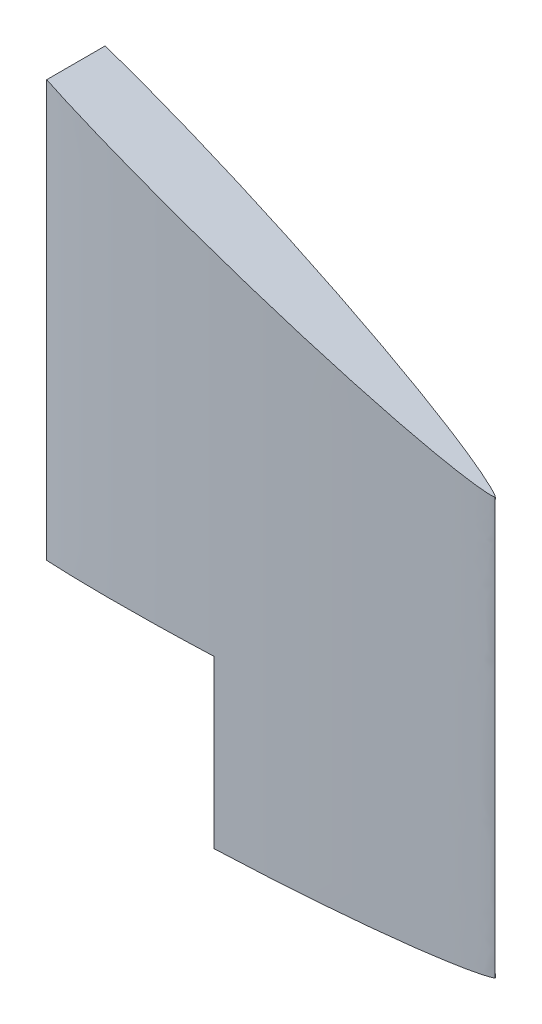
SolidWorks part; units mm, degrees
ref_plane "前视基准面" through (0, 0, 0) normal (0, 0, 1) x (1, 0, 0)
ref_plane "上视基准面" through (0, 0, 0) normal (0, 1, 0) x (1, 0, 0)
ref_plane "右视基准面" through (0, 0, 0) normal (1, 0, 0) x (0, 0, -1)
other "Configuration Table"
sketch "草图1" plane through (0, 0, 0) normal (0, 1, 0) x (1, 0, 0)
  line L0 (-2000, 0) -> (98000, 0) construction
  line L1 (0, -2000) -> (0, 98000) construction
  line L2 (0, 3.5) -> (0, -3.5)
  spline S0 degree 4 poles (50.3662, 0) (50.3616, -0.0076) (50.3512, -0.0201) (50.3319, -0.0346) (50.3036, -0.0542) (50.2676, -0.0756) (50.2125, -0.105) (50.1197, -0.1486) (49.9578, -0.2148) (49.6652, -0.3175) (49.1393, -0.4735) (48.2702, -0.6887) (46.7082, -1.0116) (44.5066, -1.3804) (41.7789, -1.7599) (38.6521, -2.1248) (35.5143, -2.4387) (32.3724, -2.71) (29.2277, -2.9446) (26.0806, -3.1456) (22.9317, -3.3152) (19.7813, -3.4544) (16.6297, -3.5633) (13.4772, -3.6409) (10.324, -3.6857) (7.1705, -3.6936) (4.1946, -3.6609) (2.0077, -3.5999) (0.6097, -3.5385) (0, -3.5) knots 0 0 0 0 0 0.000699 0.001288 0.00188 0.002733 0.003996 0.006219 0.009974 0.016536 0.028475 0.049524 0.080651 0.142462 0.204716 0.26697 0.329223 0.391477 0.453731 0.515984 0.578238 0.640492 0.702745 0.764999 0.827253 0.889506 0.95176 1 1 1 1 1 construction
  spline S1 degree 4 poles (50.3662, 0) (50.3616, -0.0076) (50.3512, -0.0201) (50.3319, -0.0346) (50.3036, -0.0542) (50.2676, -0.0756) (50.2125, -0.105) (50.1197, -0.1486) (49.9578, -0.2148) (49.6652, -0.3175) (49.1393, -0.4735) (48.2702, -0.6887) (46.7082, -1.0116) (44.5066, -1.3804) (41.7789, -1.7599) (38.6521, -2.1248) (35.5143, -2.4387) (32.3724, -2.71) (29.2277, -2.9446) (26.0806, -3.1456) (22.9317, -3.3152) (19.7813, -3.4544) (16.6297, -3.5633) (13.4772, -3.6409) (10.324, -3.6857) (7.1705, -3.6936) (4.1946, -3.6609) (2.0077, -3.5999) (0.6097, -3.5385) (0, -3.5) knots 0 0 0 0 0 0.000699 0.001288 0.00188 0.002733 0.003996 0.006219 0.009974 0.016536 0.028475 0.049524 0.080651 0.142462 0.204716 0.26697 0.329223 0.391477 0.453731 0.515984 0.578238 0.640492 0.702745 0.764999 0.827253 0.889506 0.95176 1 1 1 1 1
  spline S2 degree 4 poles (50.3662, 0) (50.3616, 0.0076) (50.3512, 0.0201) (50.3319, 0.0346) (50.3036, 0.0542) (50.2676, 0.0756) (50.2125, 0.105) (50.1197, 0.1486) (49.9578, 0.2148) (49.6652, 0.3175) (49.1393, 0.4735) (48.2702, 0.6887) (46.7082, 1.0116) (44.5066, 1.3804) (41.7789, 1.7599) (38.6521, 2.1248) (35.5143, 2.4387) (32.3724, 2.71) (29.2277, 2.9446) (26.0806, 3.1456) (22.9317, 3.3152) (19.7813, 3.4544) (16.6297, 3.5633) (13.4772, 3.6409) (10.324, 3.6857) (7.1705, 3.6936) (4.1946, 3.6609) (2.0077, 3.5999) (0.6097, 3.5385) (0, 3.5) knots 0 0 0 0 0 0.000699 0.001288 0.00188 0.002733 0.003996 0.006219 0.009974 0.016536 0.028475 0.049524 0.080651 0.142462 0.204716 0.26697 0.329223 0.391477 0.453731 0.515984 0.578238 0.640492 0.702745 0.764999 0.827253 0.889506 0.95176 1 1 1 1 1
  point P8 (0, 0)
  dimension "D1" = 7
extrude "凸台-拉伸2" add sketch "草图1" along normal blind 100
sketch "草图3" plane through (0, 0, 0) normal (0, 0, 1) x (1, 0, 0)
  line L0 (50.3662, 100) -> (50.3662, 80)
  line L1 (50.3662, 80) -> (0, 100)
  line L2 (0, 100) -> (50.3662, 100)
  line L3 (-1000, 50) -> (49000, 50) construction
  line L4 (0, 0) -> (50.3662, 0)
  line L5 (50.3662, 0) -> (50.3662, 100)
  line L6 (50.3662, 100) -> (0, 100)
  line L7 (0, 100) -> (0, 0)
  line L8 (0, 0) -> (50.3662, 0) construction
  line L9 (50.3662, 0) -> (50.3662, 100) construction
  line L10 (50.3662, 100) -> (0, 100) construction
  line L11 (0, 100) -> (0, 0) construction
  line L12 (50.3662, 0) -> (50.3662, 20)
  line L13 (0, 0) -> (50.3662, 0)
  line L14 (50.3662, 20) -> (0, 0)
  point P8 (0, 50)
  dimension "D2" = 20
  dimension "D1" = 0
extrude "切除-拉伸1" cut sketch "草图3" against normal blind 100 and the other way blind 100
sketch "草图6" plane through (0, 0, 0) normal (0, 0, 1) x (1, 0, 0)
  line L0 (-1000, 50) -> (49000, 50) construction
  line L1 (0, 50) -> (20, 50)
  line L2 (20, 50) -> (20, 30)
  line L3 (20, 30) -> (50.3662, 30)
  line L4 (0, 0) -> (50.3662, 20)
  line L5 (50.3662, 20) -> (50.3662, 80)
  line L6 (50.3662, 80) -> (0, 100)
  line L7 (0, 100) -> (0, 0)
  line L8 (0, 0) -> (50.3662, 20) construction
  line L9 (50.3662, 20) -> (50.3662, 80) construction
  line L10 (50.3662, 80) -> (0, 100) construction
  line L11 (0, 100) -> (0, 0) construction
  line L12 (50.3662, 30) -> (50.3662, 20)
  line L13 (50.3662, 20) -> (0, 0)
  line L14 (0, 0) -> (0, 50)
  point P7 (0, 50)
  dimension "D2" = 20
  dimension "D3" = 20
  dimension "D1" = 0
extrude "切除-拉伸2" cut sketch "草图6" against normal blind 100 and the other way blind 100
sketch "草图7" plane through (0, 0, 0) normal (1, 0, 0) x (0, 0, -1)
  line L4 (-3.5, 50) -> (3.5, 50)
  line L5 (-3.5, 100) -> (-3.5, 50)
  line L6 (3.5, 100) -> (-3.5, 100)
  line L7 (3.5, 50) -> (3.5, 100)
  line L8 (-3.5, 50) -> (3.5, 50) construction
  line L9 (-3.5, 100) -> (-3.5, 50) construction
  line L10 (3.5, 100) -> (-3.5, 100) construction
  line L11 (3.5, 50) -> (3.5, 100) construction
  circle A0 centre (0, 50) radius 2.5
  dimension "D2" = 5
  dimension "D1" = 0
extrude "切除-拉伸3" cut sketch "草图7" along normal blind 4
sketch "草图9" plane through (0, 0, 0) normal (0, 1, 0) x (1, 0, 0)
  line L0 (20, -1) -> (20, 1)
  line L1 (20, 3.4394) -> (20, -3.4394)
  line L2 (20, 3.4394) -> (20, -3.4394) construction
  line L3 (20, -1) -> (25, -1)
  line L4 (25, -1) -> (25, 1)
  line L5 (25, 1) -> (20, 1)
  spline S2 degree 4 poles (-426.2359, 2951.1555) (-201.3053, 23.7335) (-133.4959, 13.9087) (-51.7327, -8.1154) (29.2277, -2.9446) (32.3724, -2.71) (35.5143, -2.4387) (38.6521, -2.1248) (41.7789, -1.7599) (44.5066, -1.3804) (46.7082, -1.0116) (48.2702, -0.6887) (49.1393, -0.4735) (49.6652, -0.3175) (49.9578, -0.2148) (50.1197, -0.1486) (50.2125, -0.105) (50.2676, -0.0756) (50.3036, -0.0542) (50.7698, 0.2686) (51.1351, 1.1537) (-54.7758, 79.9279) (2083.2834, -2198.4663) knots -5.735274 -5.735274 -5.735274 -5.735274 -5.735274 0.484016 0.546269 0.608523 0.670777 0.73303 0.795284 0.857538 0.919349 0.950476 0.971525 0.983464 0.990026 0.993781 0.996004 0.997267 0.99812 0.998712 0.999301 1.042246 1.042246 1.042246 1.042246 1.042246 only from (20, -3.4394) to (50.3662, 0)
  spline S3 degree 4 poles (2081.6696, 2196.7466) (-54.7167, -79.8839) (51.135, -1.1534) (50.7697, -0.2685) (50.3036, 0.0542) (50.2676, 0.0756) (50.2125, 0.105) (50.1197, 0.1486) (49.9578, 0.2148) (49.6652, 0.3175) (49.1393, 0.4735) (48.2702, 0.6887) (46.7082, 1.0116) (44.5066, 1.3804) (41.7789, 1.7599) (38.6521, 2.1248) (35.5143, 2.4387) (32.3724, 2.71) (29.2277, 2.9446) (-51.7329, 8.1154) (-133.4961, -13.9087) (-201.3057, -23.7336) (-426.2376, -2951.1767) knots -0.042237 -0.042237 -0.042237 -0.042237 -0.042237 0.000699 0.001288 0.00188 0.002733 0.003996 0.006219 0.009974 0.016536 0.028475 0.049524 0.080651 0.142462 0.204716 0.26697 0.329223 0.391477 0.453731 0.515984 6.735285 6.735285 6.735285 6.735285 6.735285 only from (50.3662, 0) to (20, 3.4394)
  spline S4 degree 4 poles (20, -3.4394) (21.1268, -3.3943) (23.0411, -3.3088) (25.7419, -3.1672) (29.2277, -2.9446) (32.3724, -2.71) (35.5143, -2.4387) (38.6521, -2.1248) (41.7789, -1.7599) (44.5066, -1.3804) (46.7082, -1.0116) (48.2702, -0.6887) (49.1393, -0.4735) (49.6652, -0.3175) (49.9578, -0.2148) (50.1197, -0.1486) (50.2125, -0.105) (50.2676, -0.0756) (50.3036, -0.0542) (50.3319, -0.0346) (50.3512, -0.0201) (50.3616, -0.0076) (50.3662, 0) knots 0.394961 0.394961 0.394961 0.394961 0.394961 0.484016 0.546269 0.608523 0.670777 0.73303 0.795284 0.857538 0.919349 0.950476 0.971525 0.983464 0.990026 0.993781 0.996004 0.997267 0.99812 0.998712 0.999301 1 1 1 1 1 construction
  spline S5 degree 4 poles (50.3662, 0) (50.3616, 0.0076) (50.3512, 0.0201) (50.3319, 0.0346) (50.3036, 0.0542) (50.2676, 0.0756) (50.2125, 0.105) (50.1197, 0.1486) (49.9578, 0.2148) (49.6652, 0.3175) (49.1393, 0.4735) (48.2702, 0.6887) (46.7082, 1.0116) (44.5066, 1.3804) (41.7789, 1.7599) (38.6521, 2.1248) (35.5143, 2.4387) (32.3724, 2.71) (29.2277, 2.9446) (25.7419, 3.1672) (23.0411, 3.3088) (21.1268, 3.3943) (20, 3.4394) knots 0 0 0 0 0 0.000699 0.001288 0.00188 0.002733 0.003996 0.006219 0.009974 0.016536 0.028475 0.049524 0.080651 0.142462 0.204716 0.26697 0.329223 0.391477 0.453731 0.515984 0.605039 0.605039 0.605039 0.605039 0.605039 construction
  point P6 (20, 0)
  dimension "D2" = 2
  dimension "D3" = 5
  dimension "D1" = 0
extrude "切除-拉伸5" cut sketch "草图9" along normal blind 50
sketch "草图11" plane through (0, 0, 0) normal (0, 1, 0) x (1, 0, 0)
  line L0 (4, -2.5) -> (3, -2.5)
  line L1 (3, -2.5) -> (3, 2.5)
  line L2 (3, 2.5) -> (4, 2.5)
  line L3 (4, 2.5) -> (4, -2.5)
  line L4 (0, 2.5) -> (0, -2.5)
  line L5 (4, 2.5) -> (0, 2.5)
  line L6 (4, -2.5) -> (4, 2.5)
  line L7 (0, -2.5) -> (4, -2.5)
  line L8 (0, 2.5) -> (0, -2.5) construction
  line L9 (4, 2.5) -> (0, 2.5) construction
  line L10 (4, -2.5) -> (4, 2.5) construction
  line L11 (0, -2.5) -> (4, -2.5) construction
  dimension "D2" = 1
  dimension "D1" = 0
extrude "切除-拉伸6" cut sketch "草图11" along normal blind 70
